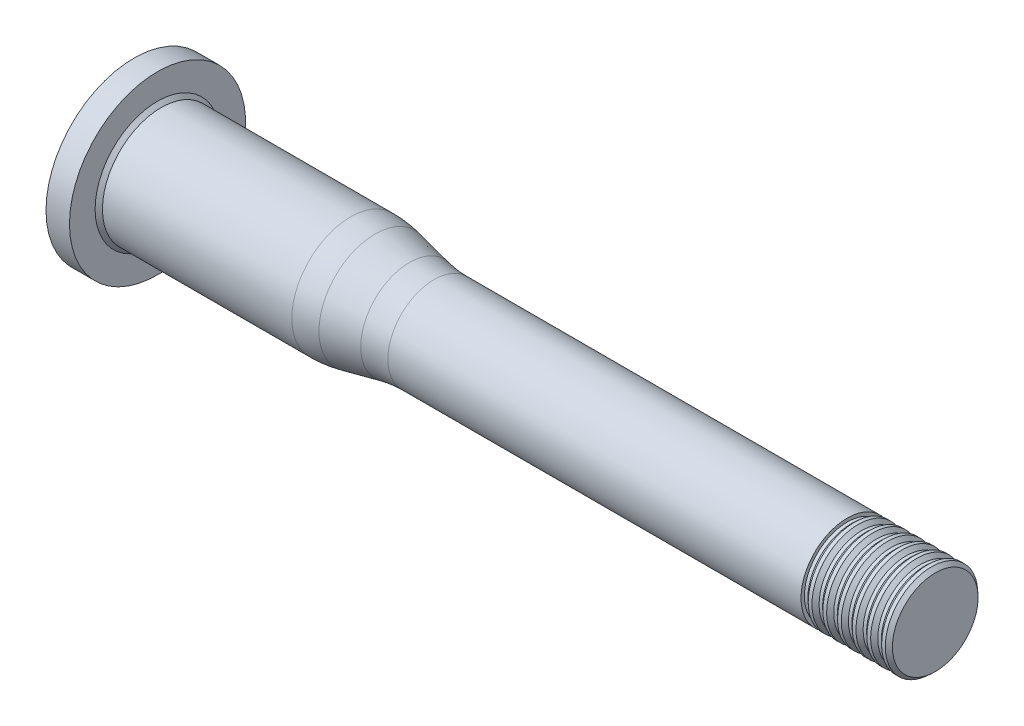
SolidWorks part; units mm, degrees
material "AISI 4130 Steel, normalized at 870C"
ref_plane "Front Plane" through (0, 0, 0) normal (0, 0, 1) x (1, 0, 0)
ref_plane "Top Plane" through (0, 0, 0) normal (0, 1, 0) x (1, 0, 0)
ref_plane "Right Plane" through (0, 0, 0) normal (1, 0, 0) x (0, 0, -1)
ref_axis "Axis1" through (0, 0, -13.97) along (0, 0, 1)
ref_axis "Axis2" through (-8.5858, 0, 0) along (1, 0, 0)
sketch "Sketch2" plane through (0, 0, 0) normal (0, 0, 1) x (1, 0, 0)
  line L1 (-5.08, 0) -> (168.275, 0)
  line L2 (-5.08, 0) -> (-5.08, 19.05)
  line L3 (-5.08, 19.05) -> (0, 19.05)
  line L4 (168.275, 0) -> (168.275, 10)
  line L5 (0, 19.05) -> (0, 12.7127)
  line L6 (0, 12.7127) -> (44.45, 12.7127)
  line L7 (0, 0) -> (182.1616, 0) construction
  line L19 (44.45, 12.7127) -> (57.15, 10)
  line L20 (57.15, 10) -> (168.275, 10)
  dimension "D2" = 38.1
  dimension "D4" = 25.4254
  dimension "D5" = 20
  dimension "D6" = 44.45
  dimension "D7" = 12.7
  dimension "D8" = 168.275
  dimension "D10" = 5.08
revolve "Revolve1" add sketch "Sketch2" angle 360 about axis through (-8.5858, 0, 0) along (1, 0, 0)
sketch "Sketch3" plane through (0, 0, 0) normal (0, 0, 1) x (1, 0, 0)
  line L0 (168.275, 9.2634) -> (167.4389, 10.0254)
  line L2 (167.4389, 10.0254) -> (166.6875, 10.0254)
  line L4 (166.6875, 10.0254) -> (165.8514, 9.2634)
  line L5 (165.8514, 9.2634) -> (165.1, 9.2634)
  line L6 (165.1, 9.2634) -> (165.1, 10.5334)
  line L7 (165.1, 10.5334) -> (168.275, 10.5334)
  line L8 (168.275, 10.5334) -> (168.275, 9.2634)
  line L9 (168.275, -10) -> (168.275, 10) construction
  line L10 (168.275, 10) -> (57.15, 10) construction
  dimension "D1" = 3.175
  dimension "D2" = 0.762
  dimension "D3" = 0.7514
  dimension "D4" = 0.0254
  dimension "D5" = 1.27
revolve "Cut-Revolve1" cut sketch "Sketch3" angle 360 about axis through (-8.5858, 0, 0) along (1, 0, 0)
pattern_linear "LPattern1" count 6 spacing 3.175 along (-1, 0, 0) of "Cut-Revolve1"
sketch "Sketch4" plane through (-5.08, 0, 0) normal (-1, 0, 0) x (0, 0, 1)
  line L1 (0, 10.9985) -> (-9.525, 5.4993)
  line L2 (-9.525, 5.4993) -> (-9.525, -5.4993)
  line L3 (-9.525, -5.4993) -> (0, -10.9985)
  line L4 (0, -10.9985) -> (9.525, -5.4993)
  line L5 (9.525, -5.4993) -> (9.525, 5.4993)
  line L6 (9.525, 5.4993) -> (0, 10.9985)
  circle A0 centre (0, 0) radius 9.525 construction
  dimension "D1" = 19.05
extrude "Cut-Extrude1" cut sketch "Sketch4" against normal blind 6.35
fillet "Fillet1" radius 25.4 2 edges at (57.15, 0, 10) (44.45, 0, 12.7127)
chamfer "Chamfer1" distance 0.7937 angle 45 1 edges at (0, 0, 12.7127)
